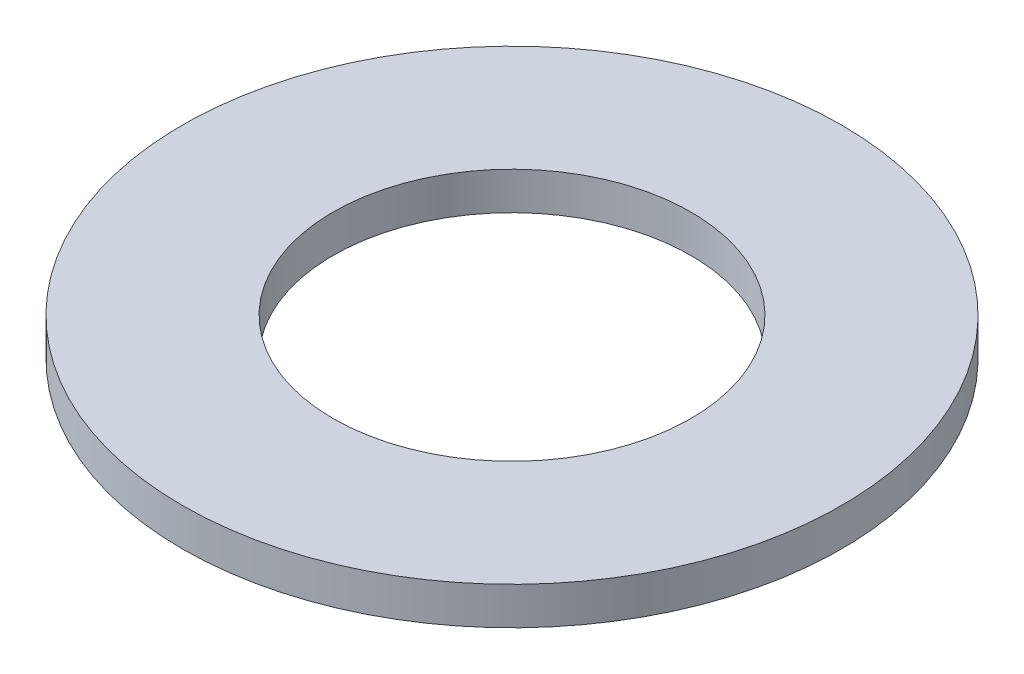
SolidWorks part; units mm, degrees
ref_plane "Front Plane" through (0, 0, 0) normal (0, 0, 1) x (1, 0, 0)
ref_plane "Top Plane" through (0, 0, 0) normal (0, 1, 0) x (1, 0, 0)
ref_plane "Right Plane" through (0, 0, 0) normal (1, 0, 0) x (0, 0, -1)
sketch "Sketch1" plane through (0, 0, 0) normal (0, 1, 0) x (1, 0, 0)
  circle A0 centre (0, 0) radius 87.5
  dimension "FLANGE_OD" = 175
extrude "Boss-Extrude1" add sketch "Sketch1" along normal blind 10
sketch "Sketch2" plane through (0, 0, 0) normal (0, 1, 0) x (1, 0, 0)
  circle A0 centre (0, 0) radius 47.5
  dimension "BORE_D" = 95
extrude "Cut-Extrude1" cut sketch "Sketch2" along normal through all
sketch "Sketch3" plane through (0, 10, 0) normal (0, 1, 0) x (1, 0, 0)
  circle A0 centre (0, 0) radius 26.1753 construction
  circle A1 centre (-26.1753, 0) radius 2.993
  dimension "BOLT_D" = 5.986
  dimension "BOLT_PCD" = 52.3506
extrude "Cut-Extrude2" cut sketch "Sketch3" against normal blind 7.001 rebuild error yes
pattern_circular "CirPattern1" count 6 over 360 rebuild error yes
